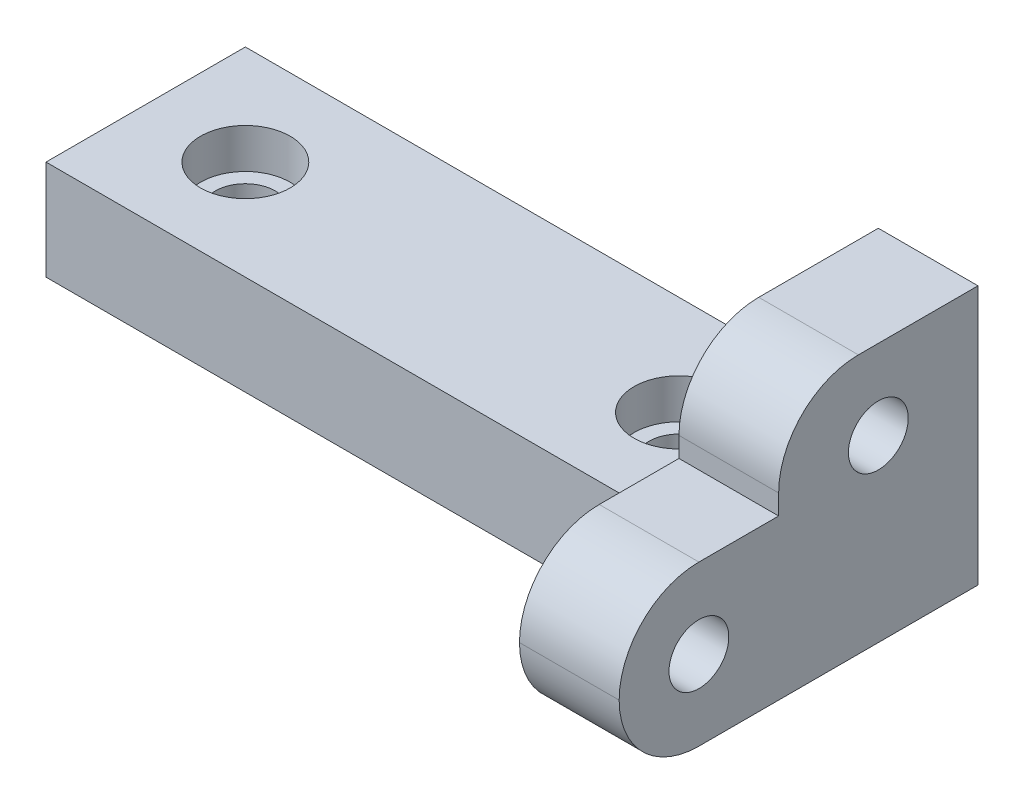
SolidWorks part; units mm, degrees
other "标注1"
sketch "草图3" plane through (0, 5, 29.5) normal (-0.6417, 0.7662, 0.0339) x (0.7661, 0.6384, 0.0747)
ref_plane "前视基准面" through (0, 0, 0) normal (0, 0, 1) x (1, 0, 0)
ref_plane "上视基准面" through (0, 0, 0) normal (0, 1, 0) x (1, 0, 0)
ref_plane "右视基准面" through (0, 0, 0) normal (1, 0, 0) x (0, 0, -1)
other "Configuration Table"
sketch "草图4" plane through (0, 0, 0) normal (0, 1, 0) x (1, 0, 0)
  line L1 (0, 0) -> (-36.75, 0)
  line L2 (0, 0) -> (0, -10)
  line L3 (0, -10) -> (-36.75, -10)
  line L4 (-36.75, 0) -> (-36.75, -10)
  line L5 (-5, 0) -> (0, 0)
  line L6 (-5, 0) -> (-5, -10)
  line L7 (-5, -10) -> (0, -10)
  line L8 (0, 0) -> (0, -10)
  dimension "D1" = 10
  dimension "D2" = 36.75
  dimension "D3" = 5
extrude "凸台-拉伸1" add sketch "草图4" along normal blind 5 contours L1 L4 L3 L2
extrude "凸台-拉伸2" add sketch "草图4<3>" along normal blind 8 from surface contours L1 L6 L3 L2 region at (-2.5, 0, 5) starting at face at (-18.375, 5, 5)
sketch "草图4<3>" plane through (0, 0, 0) normal (0, 1, 0) x (1, 0, 0) same geometry as "草图4"
sketch "草图5" plane through (0, 0, 10) normal (0, 0, 1) x (1, 0, 0)
  line L1 (-5, 13) -> (0, 13)
  line L2 (-5, 13) -> (-5, 0)
  line L3 (-5, 0) -> (0, 0)
  line L4 (0, 13) -> (0, 0)
extrude "凸台-拉伸3" add sketch "草图5" along normal blind 8
sketch "草图6" plane through (-5, 0, 0) normal (-1, 0, 0) x (0, 0, 1)
  line L1 (0, 5) -> (10, 5) construction
  line L2 (18, 0) -> (10, 0) construction
  line L3 (10, 5) -> (10, 0) construction
  line L4 (0, 13) -> (18, 13) construction
  line L5 (10, 13) -> (18, 13)
  line L6 (10, 13) -> (10, 8)
  line L7 (10, 8) -> (18, 8)
  line L8 (18, 13) -> (18, 8)
  line L9 (18, 13) -> (18, 0) construction
  circle A0 centre (5, 9) radius 2.25
  circle A1 centre (5, 9) radius 1.5
  circle A2 centre (14, 4) radius 2.25
  circle A3 centre (14, 4) radius 1.5
  point P9 (5, 5)
  dimension "D1" = 3
  dimension "D2" = 4.5
  dimension "D3" = 4
  dimension "D4" = 4
  dimension "D5" = 4
  dimension "D6" = 4
extrude "切除-拉伸1" cut sketch "草图6" against normal through all contours L5 L8 L7 L6 | A1 | A3
extrude "切除-拉伸2" cut sketch "草图6<3>" against normal blind 2 contours A0 | A2
sketch "草图6<3>" plane through (-5, 0, 0) normal (-1, 0, 0) x (0, 0, 1) same geometry as "草图6"
sketch "草图7" plane through (0, 5, 0) normal (0, 1, 0) x (1, 0, 0)
  line L1 (-36.75, 0) -> (-36.75, -10) construction
  line L2 (-36.75, -5) -> (-5, -5) construction
  line L3 (-5, 0) -> (-5, -10) construction
  circle A0 centre (-31.75, -5) radius 2.25
  circle A1 centre (-31.75, -5) radius 1.5
  circle A2 centre (-10, -5) radius 2.25
  circle A3 centre (-10, -5) radius 1.5
  point P6 (0, 0)
  dimension "D1" = 3
  dimension "D2" = 4.5
  dimension "D3" = 5
  dimension "D4" = 5
extrude "切除-拉伸3" cut sketch "草图7" against normal blind 2 contours A0 | A2
extrude "切除-拉伸4" cut sketch "草图7<3>" against normal through all contours A1 | A3
sketch "草图7<3>" plane through (0, 5, 0) normal (0, 1, 0) x (1, 0, 0) same geometry as "草图7"
fillet "圆角1" radius 4 3 edges at (-2.5, 13, 10) (-2.5, 0, 18) (-2.5, 8, 18)
